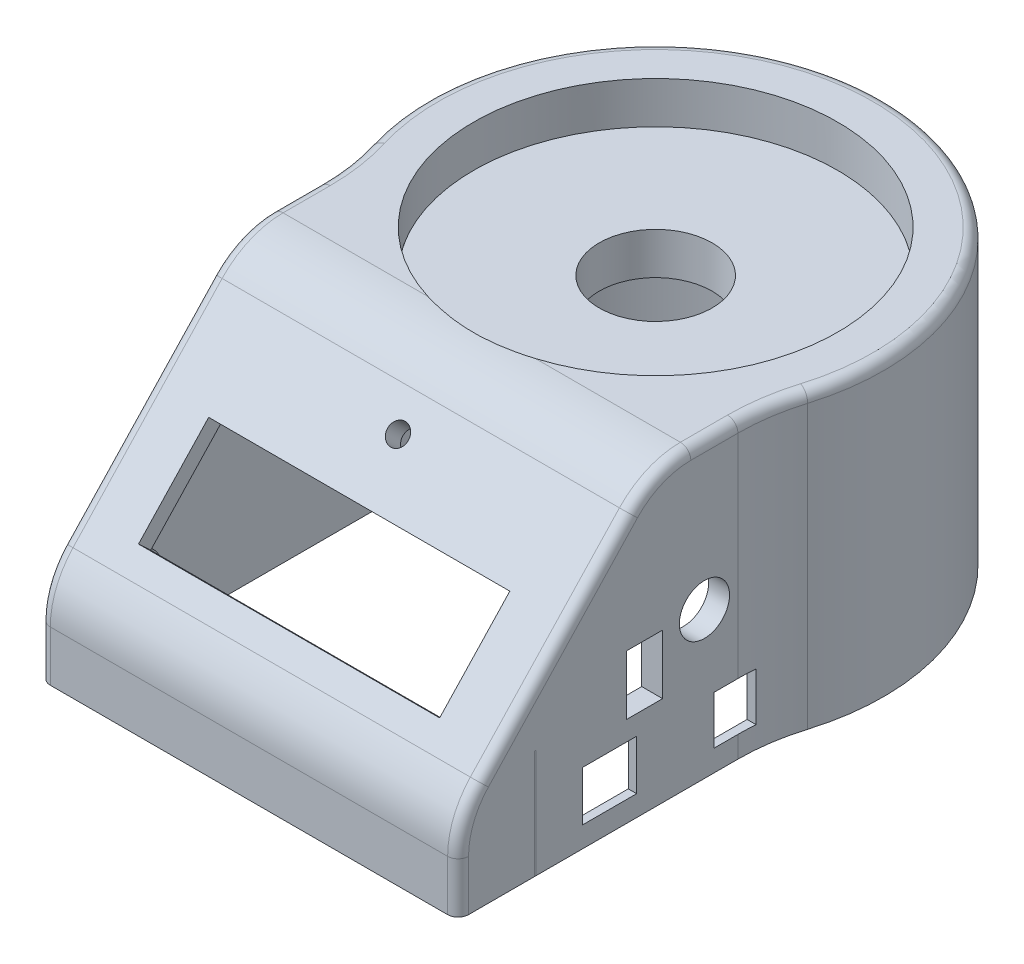
SolidWorks part; units mm, degrees
ref_plane "Front Plane" through (0, 0, 0) normal (0, 0, 1) x (1, 0, 0)
ref_plane "Top Plane" through (0, 0, 0) normal (0, 1, 0) x (1, 0, 0)
ref_plane "Right Plane" through (0, 0, 0) normal (1, 0, 0) x (0, 0, -1)
sketch "Sketch1" plane through (0, 0, 0) normal (0, 1, 0) x (1, 0, 0)
  circle A0 centre (0, 0) radius 54.5
  circle A1 centre (0, 0) radius 50
extrude "Boss-Extrude1" add sketch "Sketch1" along normal blind 60
sketch "Sketch2" plane through (0, 60, 0) normal (0, 1, 0) x (1, 0, 0)
  circle A0 centre (0, 0) radius 54.5
  circle A1 centre (0, 0) radius 43.525
extrude "Boss-Extrude2" add sketch "Sketch2" along normal blind 10
sketch "Sketch3" plane through (0, 0, 0) normal (0, -1, 0) x (1, 0, 0)
  line L0 (-50, 0) -> (-50, 97.2352)
  line L5 (-50, 97.2352) -> (50, 97.2352)
  line L6 (50, 97.2352) -> (50, 0)
  circle A0 centre (0, 0) radius 50 construction
  circle A1 centre (0, 0) radius 50 construction
  arc A3 (-50, 0) -> (50, 0) centre (0, 0) cw
extrude "Boss-Extrude4" add sketch "Sketch3" against normal blind 70 contours L6 A3 L0 L5
sketch "Sketch4" plane through (50, 0, 0) normal (1, 0, 0) x (0, 0, -1)
  line L3 (-97.2352, 70) -> (-97.2352, 20)
  line L8 (-97.2352, 70) -> (-97.2352, 0) construction
  line L9 (-97.2352, 20) -> (-97.2352, 70)
  line L10 (-97.2352, 70) -> (-50.2352, 70)
  line L11 (-97.2352, 70) -> (-21.6852, 70) construction
  line L12 (-50.2352, 70) -> (-97.2352, 20)
  dimension "D1" = 50
  dimension "D2" = 47
extrude "Cut-Extrude3" cut sketch "Sketch4" against normal blind 100 contours L10 L12 L3
shell "Shell1" thickness 5 removed face at (0, 0, 40.4139)
sketch "Sketch5" plane through (0, 0, 0) normal (0, -1, 0) x (1, 0, 0)
  line L0 (-45, 31.6228) -> (-45, 21.7945)
  line L1 (45, 31.6228) -> (45, 21.7945)
  circle A0 centre (0, 0) radius 50 construction
  arc A1 (-45, 21.7945) -> (45, 21.7945) centre (0, 0) cw
  arc A2 (-45, 31.6228) -> (45, 31.6228) centre (0, 0) cw
extrude "Cut-Extrude4" cut sketch "Sketch5" against normal blind 60
sketch "Sketch11" plane through (0, 0, 0) normal (0, -1, 0) x (1, 0, 0)
  line L0 (-50, 21.6852) -> (-50, 97.2352)
  line L1 (-50, 97.2352) -> (50, 97.2352)
  line L2 (50, 97.2352) -> (50, 21.6852)
  arc A0 (-50, 21.6852) -> (50, 21.6852) centre (0, 0) ccw
sketch "Sketch12" plane through (0, 57.9067, 61.6029) normal (0, 0.6849, 0.7286) x (1, 0, 0)
  line L0 (50, 16.5974) -> (50, -52.0248) construction
  line L1 (-36, -13.5248) -> (36, -13.5248)
  line L2 (-36, -13.5248) -> (-36, -38.0248)
  line L3 (-36, -38.0248) -> (36, -38.0248)
  line L4 (36, -13.5248) -> (36, -38.0248)
  line L5 (-50, 16.5974) -> (-50, -52.0248) construction
  line L6 (-50, -52.0248) -> (50, -52.0248) construction
  dimension "D1" = 24.5
  dimension "D2" = 72
  dimension "D3" = 14
  dimension "D4" = 14
  dimension "D5" = 14
extrude "Cut-Extrude5" cut sketch "Sketch12" against normal blind 4
sketch "Sketch13" plane through (0, 54.4822, 57.9597) normal (0, -0.6849, -0.7286) x (-1, 0, 0)
  line L1 (-40, -7.0248) -> (40, -7.0248)
  line L2 (-40, -7.0248) -> (-40, -43.0248)
  line L3 (-40, -43.0248) -> (40, -43.0248)
  line L4 (40, -7.0248) -> (40, -43.0248)
  line L6 (-36, -13.5248) -> (36, -13.5248) construction
  line L7 (36, -38.0248) -> (-36, -38.0248) construction
  line L8 (-36, -38.0248) -> (-36, -13.5248) construction
  dimension "D1" = 80
  dimension "D2" = 36
  dimension "D3" = 6.5
  dimension "D4" = 5
  dimension "D5" = 4
extrude "Cut-Extrude6" cut sketch "Sketch13" against normal up to vertex (1 mm away) up to point (36, 45.3125, 67.9516)
sketch "Sketch15" plane through (0, 57.9067, 61.6029) normal (0, 0.6849, 0.7286) x (1, 0, 0)
  line L0 (-40, -7.0248) -> (40, -7.0248) construction
  line L1 (-40, -43.0248) -> (-40, -7.0248) construction
  line L2 (40, -43.0248) -> (-40, -43.0248) construction
  line L3 (40, -7.0248) -> (40, -43.0248) construction
  circle A0 centre (-37.5, -9.5248) radius 2.75
  circle A1 centre (37.5, -9.5248) radius 2.75
  circle A2 centre (-37.5, -40.5248) radius 2.75
  circle A3 centre (37.5, -40.5248) radius 2.75
  dimension "D1" = 2.5
  dimension "D2" = 2.5
  dimension "D3" = 2.5
  dimension "D4" = 2.5
  dimension "D5" = 2.5
  dimension "D6" = 2.5
  dimension "D7" = 2.5
  dimension "D8" = 2.5
extrude "Boss-Extrude5" add sketch "Sketch15" against normal blind 7
hole_wizard "M3 Clearance Hole1" positions "Sketch16" profile "Sketch17" hole size "M3" standard "ANSI Metric"
sketch "Sketch16" plane through (0, 53.1123, 56.5025) normal (0, -0.6849, -0.7286) x (-1, 0, 0)
  point P0 (-37.5, -9.5248)
  point P3 (37.5, -9.5248)
  point P6 (37.5, -40.5248)
  point P9 (-37.5, -40.5248)
sketch "Sketch17" plane through (37.5, 46.1723, 63.0261) normal (1, 0, 0) x (0, 0.7286, -0.6849)
  line L0 (0, 0) -> (0, 6.0215)
  line L1 (0, 6.0215) -> (1.7, 5)
  line L2 (1.7, 5) -> (1.7, 0.025)
  line L3 (1.7, 0.025) -> (1.725, 0)
  line L5 (1.725, 0) -> (0, 0)
  line L6 (-1.7, 0.025) -> (-1.725, 0) construction
  line L10 (0, 6.0215) -> (-1.7, 5) construction
  line L11 (0, -6.35) -> (0, 107.95) construction
  dimension "Hole Dia." = 3.4
  dimension "Hole Depth" = 5
  dimension "Near C'Sink Dia." = 3.45
  dimension "Near C'Sink Angle" = 90
  dimension "Drill Angle" = 118
sketch "Sketch19" plane through (0, 0, 0) normal (0, -1, 0) x (-1, 0, 0)
  line L0 (50, -97.2352) -> (-50, -97.2352) construction
  line L1 (50, -21.6852) -> (50, -97.2352) construction
  line L2 (-50, -97.2352) -> (-50, -21.6852) construction
  circle A0 centre (40, -87.2352) radius 5
  circle A1 centre (-40, -87.2352) radius 5
  dimension "D1" = 10
  dimension "D2" = 10
  dimension "D3" = 10
  dimension "D4" = 10
extrude "Boss-Extrude6" add sketch "Sketch19" against normal blind 15 separate body
sketch "Sketch20" plane through (0, 0, 0) normal (0, -1, 0) x (1, 0, 0)
  line L0 (-40, 92.2352) -> (-45, 92.2352)
  line L1 (-45, 92.2352) -> (45, 92.2352) construction
  line L2 (-45, 92.2352) -> (-45, 87.2352)
  line L3 (-45, 21.7945) -> (-45, 92.2352) construction
  line L4 (45, 92.2352) -> (45, 21.7945) construction
  line L5 (40, 92.2352) -> (45, 92.2352)
  line L6 (-45, 92.2352) -> (45, 92.2352) construction
  line L7 (45, 92.2352) -> (45, 87.2352)
  circle A0 centre (-40, 87.2352) radius 5 construction
  arc A1 (-45, 87.2352) -> (-40, 92.2352) centre (-40, 87.2352) cw
  arc A2 (40, 92.2352) -> (45, 87.2352) centre (40, 87.2352) cw
  circle A3 centre (40, 87.2352) radius 5 construction
extrude "Boss-Extrude7" add sketch "Sketch20" against normal blind 15
sketch "Sketch21" plane through (0, 0, 0) normal (0, -1, 0) x (1, 0, 0)
  line L0 (50, 97.2352) -> (50, 21.6852) construction
  circle A0 centre (47, 1.6852) radius 5
  circle A1 centre (-47, 1.6852) radius 5
  dimension "D1" = 20
  dimension "D2" = 3
  dimension "D3" = 20
  dimension "D4" = 3
extrude "Boss-Extrude8" add sketch "Sketch21" against normal blind 15
hole_wizard "Tap Drill for M4x0.7 Tap1" positions "3DSketch1" profile "Sketch23" hole size "M4x0.7" standard "ANSI Metric" end condition up to next
sketch3d "3DSketch1"
  line L0 (-47, 15, 1.6852) -> (-47, 0, 1.6852) construction
  line L1 (47, 15, 1.6852) -> (47, 0, 1.6852) construction
  line L2 (40, 15, 87.2352) -> (40, 0, 87.2352) construction
  line L3 (-40, 15, 87.2352) -> (-40, 0, 87.2352) construction
  point P0 (-47, 0, 1.6852)
  point P4 (47, 0, 1.6852)
  point P8 (40, 0, 87.2352)
  point P12 (-40, 0, 87.2352)
sketch "Sketch23" plane through (-47, 0, 1.6852) normal (1, 0, 0) x (0, 0, -1)
  line L0 (0, 0) -> (0, 15)
  line L1 (0, 15) -> (1.65, 15)
  line L2 (1.65, 15) -> (1.65, 0.025)
  line L3 (1.65, 0.025) -> (1.675, 0)
  line L5 (1.675, 0) -> (0, 0)
  line L6 (-1.65, 0.025) -> (-1.675, 0) construction
  line L11 (0, -6.35) -> (0, 107.95) construction
  dimension "Thru Hole Dia." = 3.3
  dimension "Thru Hole Depth" = 15
  dimension "Near C'Sink Dia." = 3.35
  dimension "Near C'Sink Angle" = 90
sketch "Sketch24" plane through (50, 0, 0) normal (1, 0, 0) x (0, 0, -1)
  line L1 (-21.6852, 0) -> (-78.9852, 0)
  line L2 (-21.6852, 0) -> (-21.6852, 26)
  line L3 (-21.6852, 26) -> (-78.9852, 26)
  line L4 (-78.9852, 0) -> (-78.9852, 26)
  dimension "D1" = 26
  dimension "D2" = 57.3
extrude "Cut-Extrude7" cut sketch "Sketch24" against normal blind 5
sketch "Sketch25" plane through (50, 0, 50) normal (1, 0, 0) x (0, 0, 1)
  line L1 (-28.6534, -26) -> (28.6466, -26)
  line L2 (-28.6534, -26) -> (-28.6534, 0)
  line L3 (-28.6534, 0) -> (28.6466, 0)
  line L4 (28.6466, -26) -> (28.6466, 0)
  line L5 (4.5466, -4.96) -> (17.5466, -4.96)
  line L6 (4.5466, -4.96) -> (4.5466, -16.86)
  line L7 (4.5466, -16.86) -> (17.5466, -16.86)
  line L8 (17.5466, -4.96) -> (17.5466, -16.86)
  line L9 (-23.8534, -5.13) -> (-13.9534, -5.13)
  line L10 (-23.8534, -5.13) -> (-23.8534, -16.69)
  line L11 (-23.8534, -16.69) -> (-13.9534, -16.69)
  line L12 (-13.9534, -5.13) -> (-13.9534, -16.69)
  dimension "D1" = 4.8
  dimension "D2" = 9.9
  dimension "D3" = 11.5599
  dimension "D4" = 13
  dimension "D5" = 11.9
  dimension "D6" = 11.1
  dimension "D7" = 9.31
  dimension "D8" = 9.14
extrude "Boss-Extrude9" add sketch "Sketch25" against normal blind 2
sketch "Sketch26" plane through (50, 0, 0) normal (1, 0, 0) x (0, 0, -1)
  line L1 (-78.9852, 26) -> (-78.6466, 26)
  line L2 (-78.9852, 26) -> (-78.9852, 0)
  line L3 (-78.9852, 0) -> (-78.6466, 0)
  line L4 (-78.6466, 26) -> (-78.6466, 0)
extrude "Boss-Extrude10" add sketch "Sketch26" against normal blind 2 separate body
fillet "Fillet1" radius 50 2 edges at (50, 35, 21.6852) (-50, 35, 21.6852)
fillet "Fillet2" radius 20 1 edges at (0, 20, 97.2352)
fillet "Fillet3" radius 20 1 edges at (0, 70, 50.2352)
fillet "Fillet4" radius 2.5 13 edges at (-50, 6.0378, 97.2352) (-50, 19.4428, 95.8289) (50, 6.0378, 97.2352) (50, 19.4428, 95.8289) (50, 44.736, 73.9833) (-50, 44.736, 73.9833) (-50, 68.3571, 49.5247) (-50, 70, 35.961) (-50.5412, 70, 22.9989) (0, 70, -54.5) (50.5412, 70, 22.9989) (50, 70, 35.961) (50, 68.3571, 49.5247)
sketch "Sketch27" plane through (0, 54.4822, 57.9597) normal (0, -0.6849, -0.7286) x (-1, 0, 0)
  circle A0 centre (0, 0) radius 2.5
  point P0 (0, 0)
extrude "Cut-Extrude8" cut sketch "Sketch27" against normal up to next (5 mm away)
sketch "Sketch28" plane through (50, 0, 0) normal (1, 0, 0) x (0, 0, -1)
  line L0 (-21.6852, 0) -> (-97.2352, 0) construction
  line L1 (-30.3356, 0) -> (-30.3356, 5.13) construction
  point P0 (-38.3356, 35)
  dimension "D1" = 35
  dimension "D2" = 8
hole_wizard "Hole1" positions "3DSketch2" profile "Sketch30" legacy end condition up to next
sketch3d "3DSketch2"
  point P0 (50, 35, 38.3356)
sketch "Sketch30" plane through (50, 35, 38.3356) normal (0, 1, 0) x (0, 0, -1)
  line L0 (0, 0) -> (0, 5.001)
  line L1 (0, 5.001) -> (6, 5.001)
  line L2 (6, 5.001) -> (6, 0)
  line L3 (6, 0) -> (0, 0)
  line L4 (0, 110) -> (0, -10) construction
  dimension "Diameter" = 12
  dimension "Depth" = 5.001
sketch "Sketch31" plane through (0, 60, 0) normal (0, -1, 0) x (1, 0, 0)
  circle A0 centre (0, 0) radius 13.5
  circle A1 centre (0, 0) radius 43.525
extrude "Boss-Extrude11" add sketch "Sketch31" along normal blind 10 separate body
sketch "Sketch32" plane through (0, 60, 0) normal (0, -1, 0) x (1, 0, 0)
  line L0 (-45, 21.7945) -> (-37.6753, 21.7945)
  line L1 (37.6753, 21.7945) -> (45, 21.7945)
  arc A0 (-45, 21.7945) -> (45, 21.7945) centre (0, 0) ccw
  arc A1 (-45, 21.7945) -> (45, 21.7945) centre (0, 0) ccw construction
  arc A2 (-37.6753, 21.7945) -> (37.6753, 21.7945) centre (0, 0) ccw
  circle A3 centre (0, 0) radius 43.525 construction
extrude "Boss-Extrude16" add sketch "Sketch32" along normal blind 10 separate body
sketch "Sketch33" plane through (50, 0, 0) normal (1, 0, 0) x (0, 0, -1)
  line L1 (-56.9356, 35.7345) -> (-48.3356, 35.7345)
  line L2 (-56.9356, 35.7345) -> (-56.9356, 21.5345)
  line L3 (-56.9356, 21.5345) -> (-48.3356, 21.5345)
  line L4 (-48.3356, 35.7345) -> (-48.3356, 21.5345)
  circle A0 centre (-38.3356, 35) radius 6 construction
  dimension "D3" = 10
  dimension "D1" = 14.2
  dimension "D2" = 8.6
sketch "Sketch36" plane through (0, 26, 0) normal (0, -1, 0) x (1, 0, 0)
  line L1 (45, 78.9852) -> (48, 78.9852)
  line L2 (45, 78.9852) -> (45, 21.6852)
  line L3 (45, 21.6852) -> (48, 21.6852)
  line L4 (48, 78.9852) -> (48, 21.6852)
extrude "Boss-Extrude17" add sketch "Sketch36" along normal blind 8
extrude "Cut-Extrude10" cut sketch "Sketch33" against normal blind 8
